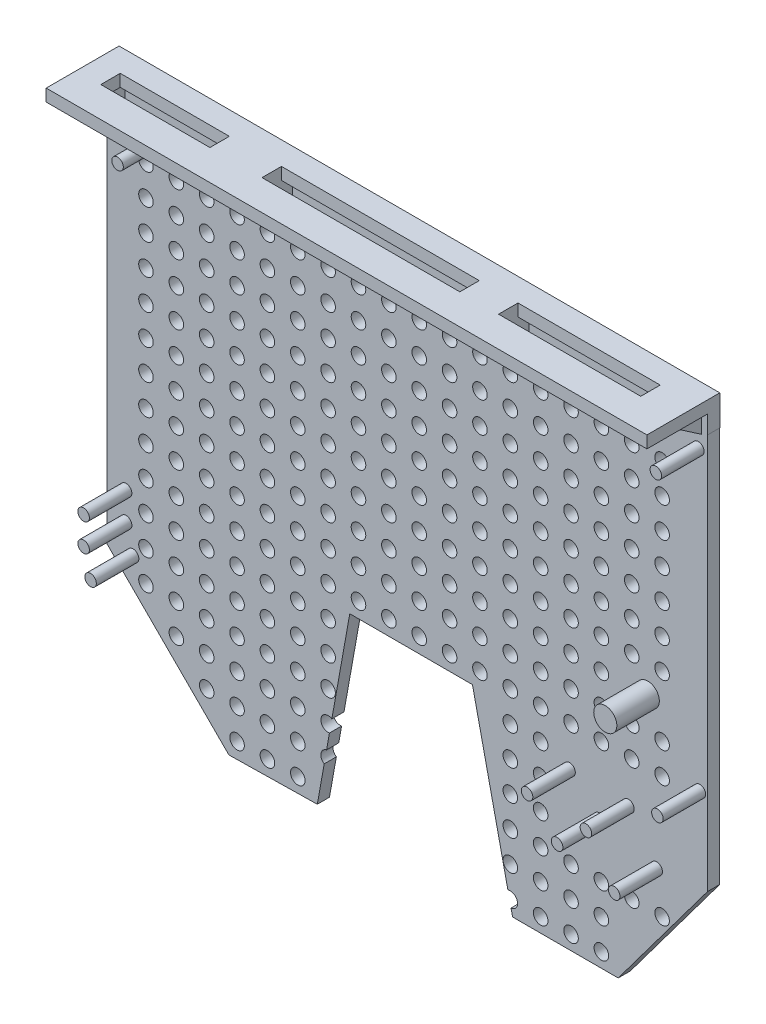
SolidWorks part; units mm, degrees
ref_plane "前视基准面" through (0, 0, 0) normal (0, 0, 1) x (1, 0, 0)
ref_plane "上视基准面" through (0, 0, 0) normal (0, 1, 0) x (1, 0, 0)
ref_plane "右视基准面" through (0, 0, 0) normal (1, 0, 0) x (0, 0, -1)
sketch "草图1" plane through (0, 0, 0) normal (0, 0, 1) x (1, 0, 0)
  line B0 (-29.0704, -45.0482) -> (-8.9847, -65.1339)
  line B1 (-29.0704, 19.934) -> (69.8393, 19.934)
  line B2 (-29.0704, 19.934) -> (-29.0704, -45.0482)
  line B3 (69.8393, 19.934) -> (69.8393, -45.2054)
  line B4 (5.5774, -64.8844) -> (10.922, -35.0394)
  line B5 (10.922, -35.0394) -> (31.1275, -35.0494)
  line B6 (31.1275, -35.0494) -> (37.7318, -64.8844)
  line B7 (37.7318, -64.8844) -> (55.1271, -64.8881)
  line B8 (55.1271, -64.8881) -> (69.8393, -45.2054)
  line B9 (-8.9847, -65.1339) -> (5.5774, -64.8844)
  circle B10 centre (-24.765, -44.5771) radius 0.95
sketch_block_instance "块-草图1-1"
sketch_block "块-草图1"
extrude "凸台-拉伸1" add sketch "草图1" along normal blind 2 contours B2 B0 B9 B4 B5 B6 B7 B8 B3 B1
sketch "草图2" plane through (0, 0, 0) normal (0, 0, 1) x (1, 0, 0)
  line B0 (-29.0704, -45.0482) -> (-8.9847, -65.1339)
  line B1 (-29.0704, 19.934) -> (69.8393, 19.934)
  line B2 (-29.0704, 19.934) -> (-29.0704, -45.0482)
  line B3 (69.8393, 19.934) -> (69.8393, -45.2054)
  line B4 (5.5774, -64.8844) -> (10.922, -35.0394)
  line B5 (10.922, -35.0394) -> (31.1275, -35.0494)
  line B6 (31.1275, -35.0494) -> (37.7318, -64.8844)
  line B7 (37.7318, -64.8844) -> (55.1271, -64.8881)
  line B8 (55.1271, -64.8881) -> (69.8393, -45.2054)
  line B9 (-8.9847, -65.1339) -> (5.5774, -64.8844)
  circle B10 centre (-20.32, 17.018) radius 0.95
  circle B11 centre (68.3261, 17.272) radius 0.95
  circle B12 centre (60.0001, -22) radius 1.9
  circle B13 centre (68.5801, -31.4961) radius 0.95
  circle B14 centre (-25.9081, -35.8141) radius 0.95
  circle B15 centre (-25.9081, -40.3861) radius 0.95
  circle B16 centre (-24.765, -44.5771) radius 0.95
  circle B17 centre (56.8115, -39.4971) radius 0.95
  circle B18 centre (47.1171, -39.1161) radius 0.95
  circle B19 centre (52.0701, -43.8151) radius 0.95
  circle B20 centre (61.4681, -46.1011) radius 0.95
sketch_block_instance "块-草图1-2"
extrude "凸台-拉伸2" add sketch "草图2" along normal blind 9 contours B10 | B11 | B12 | B13 | B17 | B19 | B18 | B16 | B14 | B15 | B20
sketch "草图3" plane through (0, 0, 0) normal (0, 0, 1) x (1, 0, 0)
  line L1 (-29.0704, 19.934) -> (69.8586, 19.934)
  line L2 (-29.0704, 19.934) -> (-29.0704, 24.934)
  line L3 (-29.0704, 24.934) -> (69.8586, 24.934)
  line L4 (69.8586, 19.934) -> (69.8586, 24.934)
  line B0 (-29.0704, -45.0482) -> (-8.9847, -65.1339)
  line B1 (-29.0704, 19.934) -> (69.8393, 19.934)
  line B2 (-29.0704, 19.934) -> (-29.0704, -45.0482)
  line B3 (69.8393, 19.934) -> (69.8393, -45.2054)
  line B4 (5.5774, -64.8844) -> (10.922, -35.0394)
  line B5 (10.922, -35.0394) -> (31.1275, -35.0494)
  line B6 (31.1275, -35.0494) -> (37.7318, -64.8844)
  line B7 (37.7318, -64.8844) -> (55.1271, -64.8881)
  line B8 (55.1271, -64.8881) -> (69.8393, -45.2054)
  line B9 (-8.9847, -65.1339) -> (5.5774, -64.8844)
  circle B10 centre (-20.32, 17.018) radius 0.95
  circle B11 centre (68.3261, 17.272) radius 0.95
  circle B12 centre (60.0001, -22) radius 1.9
  circle B13 centre (68.5801, -31.4961) radius 0.95
  circle B14 centre (-25.9081, -35.8141) radius 0.95
  circle B15 centre (-25.9081, -40.3861) radius 0.95
  circle B16 centre (-24.765, -44.5771) radius 0.95
  circle B17 centre (56.8115, -39.4971) radius 0.95
  circle B18 centre (47.1171, -39.1161) radius 0.95
  circle B19 centre (52.0701, -43.8151) radius 0.95
  circle B20 centre (61.4681, -46.1011) radius 0.95
  dimension "D1" = 5
sketch_block_instance "块-草图1-3"
extrude "凸台-拉伸3" add sketch "草图3" along normal blind 2 contours L3 L4 L1 L2
sketch "草图4" plane through (0, 0, 0) normal (0, 0, 1) x (1, 0, 0)
  line L1 (-29.0704, 19.934) -> (69.8586, 19.934)
  line L2 (-29.0704, 19.934) -> (-29.0704, 24.934)
  line L3 (-29.0704, 24.934) -> (69.8586, 24.934)
  line L4 (69.8586, 19.934) -> (69.8586, 24.934)
  line L5 (69.8586, 24.934) -> (-29.0704, 24.934)
  line L6 (69.8586, 24.934) -> (69.8586, 22.934)
  line L7 (69.8586, 22.934) -> (-29.0704, 22.934)
  line L8 (-29.0704, 24.934) -> (-29.0704, 22.934)
  line B0 (-29.0704, -45.0482) -> (-8.9847, -65.1339)
  line B1 (-29.0704, 19.934) -> (69.8393, 19.934)
  line B2 (-29.0704, 19.934) -> (-29.0704, -45.0482)
  line B3 (69.8393, 19.934) -> (69.8393, -45.2054)
  line B4 (5.5774, -64.8844) -> (10.922, -35.0394)
  line B5 (10.922, -35.0394) -> (31.1275, -35.0494)
  line B6 (31.1275, -35.0494) -> (37.7318, -64.8844)
  line B7 (37.7318, -64.8844) -> (55.1271, -64.8881)
  line B8 (55.1271, -64.8881) -> (69.8393, -45.2054)
  line B9 (-8.9847, -65.1339) -> (5.5774, -64.8844)
  circle B10 centre (-20.32, 17.018) radius 0.95
  circle B11 centre (68.3261, 17.272) radius 0.95
  circle B12 centre (60.0001, -22) radius 1.9
  circle B13 centre (68.5801, -31.4961) radius 0.95
  circle B14 centre (-25.9081, -35.8141) radius 0.95
  circle B15 centre (-25.9081, -40.3861) radius 0.95
  circle B16 centre (-24.765, -44.5771) radius 0.95
  circle B17 centre (56.8115, -39.4971) radius 0.95
  circle B18 centre (47.1171, -39.1161) radius 0.95
  circle B19 centre (52.0701, -43.8151) radius 0.95
  circle B20 centre (61.4681, -46.1011) radius 0.95
  dimension "D1" = 5
  dimension "D2" = 2
sketch_block_instance "块-草图1-4"
extrude "凸台-拉伸4" add sketch "草图4" along normal blind 12 contours L6 L7 L8 L3
ref_plane "基准面2" through (0, 24.934, 0) normal (0, 1, 0) x (1, 0, 0)
sketch "草图6" plane through (0, 24.934, 0) normal (0, 1, 0) x (1, 0, 0)
  line L0 (69.8586, -12) -> (69.8586, 0) construction
  line L1 (-29.0704, -12) -> (69.8586, -12)
  line L2 (-29.0704, -12) -> (-29.0704, -7)
  line L3 (-29.0704, -7) -> (69.8586, -7)
  line L4 (69.8586, -12) -> (69.8586, -7)
  line L6 (1.4708, -7) -> (34.0493, -7)
  line L7 (1.4708, -7) -> (1.4708, -3.8)
  line L8 (1.4708, -3.8) -> (34.0493, -3.8)
  line L9 (34.0493, -7) -> (34.0493, -3.8)
  line L10 (40.4259, -7) -> (63.8453, -7)
  line L11 (40.4259, -7) -> (40.4259, -3.8)
  line L12 (40.4259, -3.8) -> (63.8453, -3.8)
  line L13 (63.8453, -7) -> (63.8453, -3.8)
  line L14 (-7.1086, -7) -> (-25.0789, -7)
  line L15 (-7.1086, -7) -> (-7.1086, -3.8)
  line L16 (-7.1086, -3.8) -> (-25.0789, -3.8)
  line L17 (-25.0789, -7) -> (-25.0789, -3.8)
  dimension "D1" = 5
  dimension "D2" = 3.2
extrude "切除-拉伸3" cut sketch "草图6" against normal up to next contours L11 L12 L13 L10 | L7 L8 L9 L6 | L16 L17 L14 L15
sketch "草图8" plane through (0, 0, 0) normal (0, 0, 1) x (1, 0, 0)
  circle A38 centre (-12.6417, 17.4584) radius 1.2
  circle A39 centre (-7.6417, 17.4584) radius 1.2
  circle A40 centre (-2.6417, 17.4584) radius 1.2
  circle A41 centre (2.3583, 17.4584) radius 1.2
  circle A42 centre (7.3583, 17.4584) radius 1.2
  circle A43 centre (12.3583, 17.4584) radius 1.2
  circle A44 centre (17.3583, 17.4584) radius 1.2
  circle A45 centre (22.3583, 17.4584) radius 1.2
  circle A46 centre (27.3583, 17.4584) radius 1.2
  circle A47 centre (32.3583, 17.4584) radius 1.2
  circle A48 centre (37.3583, 17.4584) radius 1.2
  circle A49 centre (42.3583, 17.4584) radius 1.2
  circle A50 centre (47.3583, 17.4584) radius 1.2
  circle A51 centre (52.3583, 17.4584) radius 1.2
  circle A52 centre (57.3583, 17.4584) radius 1.2
  circle A53 centre (62.3583, 17.4584) radius 1.2
  circle A54 centre (-17.6417, 12.4584) radius 1.2
  circle A55 centre (-12.6417, 12.4584) radius 1.2
  circle A56 centre (-7.6417, 12.4584) radius 1.2
  circle A57 centre (-2.6417, 12.4584) radius 1.2
  circle A58 centre (2.3583, 12.4584) radius 1.2
  circle A59 centre (7.3583, 12.4584) radius 1.2
  circle A60 centre (12.3583, 12.4584) radius 1.2
  circle A61 centre (17.3583, 12.4584) radius 1.2
  circle A62 centre (22.3583, 12.4584) radius 1.2
  circle A63 centre (27.3583, 12.4584) radius 1.2
  circle A64 centre (32.3583, 12.4584) radius 1.2
  circle A65 centre (37.3583, 12.4584) radius 1.2
  circle A66 centre (42.3583, 12.4584) radius 1.2
  circle A67 centre (47.3583, 12.4584) radius 1.2
  circle A68 centre (52.3583, 12.4584) radius 1.2
  circle A69 centre (57.3583, 12.4584) radius 1.2
  circle A70 centre (62.3583, 12.4584) radius 1.2
  circle A71 centre (-17.6417, 7.4584) radius 1.2
  circle A72 centre (-12.6417, 7.4584) radius 1.2
  circle A73 centre (-7.6417, 7.4584) radius 1.2
  circle A74 centre (-2.6417, 7.4584) radius 1.2
  circle A75 centre (2.3583, 7.4584) radius 1.2
  circle A76 centre (7.3583, 7.4584) radius 1.2
  circle A77 centre (12.3583, 7.4584) radius 1.2
  circle A78 centre (17.3583, 7.4584) radius 1.2
  circle A79 centre (22.3583, 7.4584) radius 1.2
  circle A80 centre (27.3583, 7.4584) radius 1.2
  circle A81 centre (32.3583, 7.4584) radius 1.2
  circle A82 centre (37.3583, 7.4584) radius 1.2
  circle A83 centre (42.3583, 7.4584) radius 1.2
  circle A84 centre (47.3583, 7.4584) radius 1.2
  circle A85 centre (52.3583, 7.4584) radius 1.2
  circle A86 centre (57.3583, 7.4584) radius 1.2
  circle A87 centre (62.3583, 7.4584) radius 1.2
  circle A88 centre (-17.6417, 2.4584) radius 1.2
  circle A89 centre (-12.6417, 2.4584) radius 1.2
  circle A90 centre (-7.6417, 2.4584) radius 1.2
  circle A91 centre (-2.6417, 2.4584) radius 1.2
  circle A92 centre (2.3583, 2.4584) radius 1.2
  circle A93 centre (7.3583, 2.4584) radius 1.2
  circle A94 centre (12.3583, 2.4584) radius 1.2
  circle A95 centre (17.3583, 2.4584) radius 1.2
  circle A96 centre (22.3583, 2.4584) radius 1.2
  circle A97 centre (27.3583, 2.4584) radius 1.2
  circle A98 centre (32.3583, 2.4584) radius 1.2
  circle A99 centre (37.3583, 2.4584) radius 1.2
  circle A100 centre (42.3583, 2.4584) radius 1.2
  circle A101 centre (47.3583, 2.4584) radius 1.2
  circle A102 centre (52.3583, 2.4584) radius 1.2
  circle A103 centre (57.3583, 2.4584) radius 1.2
  circle A104 centre (62.3583, 2.4584) radius 1.2
  circle A105 centre (-17.6417, -2.5416) radius 1.2
  circle A106 centre (-12.6417, -2.5416) radius 1.2
  circle A107 centre (-7.6417, -2.5416) radius 1.2
  circle A108 centre (-2.6417, -2.5416) radius 1.2
  circle A109 centre (2.3583, -2.5416) radius 1.2
  circle A110 centre (7.3583, -2.5416) radius 1.2
  circle A111 centre (12.3583, -2.5416) radius 1.2
  circle A112 centre (17.3583, -2.5416) radius 1.2
  circle A113 centre (22.3583, -2.5416) radius 1.2
  circle A114 centre (27.3583, -2.5416) radius 1.2
  circle A115 centre (32.3583, -2.5416) radius 1.2
  circle A116 centre (37.3583, -2.5416) radius 1.2
  circle A117 centre (42.3583, -2.5416) radius 1.2
  circle A118 centre (47.3583, -2.5416) radius 1.2
  circle A119 centre (52.3583, -2.5416) radius 1.2
  circle A120 centre (57.3583, -2.5416) radius 1.2
  circle A121 centre (62.3583, -2.5416) radius 1.2
  circle A122 centre (-17.6417, -7.5416) radius 1.2
  circle A123 centre (-12.6417, -7.5416) radius 1.2
  circle A124 centre (-7.6417, -7.5416) radius 1.2
  circle A125 centre (-2.6417, -7.5416) radius 1.2
  circle A126 centre (2.3583, -7.5416) radius 1.2
  circle A127 centre (7.3583, -7.5416) radius 1.2
  circle A128 centre (12.3583, -7.5416) radius 1.2
  circle A129 centre (17.3583, -7.5416) radius 1.2
  circle A130 centre (22.3583, -7.5416) radius 1.2
  circle A131 centre (27.3583, -7.5416) radius 1.2
  circle A132 centre (32.3583, -7.5416) radius 1.2
  circle A133 centre (37.3583, -7.5416) radius 1.2
  circle A134 centre (42.3583, -7.5416) radius 1.2
  circle A135 centre (47.3583, -7.5416) radius 1.2
  circle A136 centre (52.3583, -7.5416) radius 1.2
  circle A137 centre (57.3583, -7.5416) radius 1.2
  circle A138 centre (62.3583, -7.5416) radius 1.2
  circle A139 centre (-17.6417, -12.5416) radius 1.2
  circle A140 centre (-12.6417, -12.5416) radius 1.2
  circle A141 centre (-7.6417, -12.5416) radius 1.2
  circle A142 centre (-2.6417, -12.5416) radius 1.2
  circle A143 centre (2.3583, -12.5416) radius 1.2
  circle A144 centre (7.3583, -12.5416) radius 1.2
  circle A145 centre (12.3583, -12.5416) radius 1.2
  circle A146 centre (17.3583, -12.5416) radius 1.2
  circle A147 centre (22.3583, -12.5416) radius 1.2
  circle A148 centre (27.3583, -12.5416) radius 1.2
  circle A149 centre (32.3583, -12.5416) radius 1.2
  circle A150 centre (37.3583, -12.5416) radius 1.2
  circle A151 centre (42.3583, -12.5416) radius 1.2
  circle A152 centre (47.3583, -12.5416) radius 1.2
  circle A153 centre (52.3583, -12.5416) radius 1.2
  circle A154 centre (57.3583, -12.5416) radius 1.2
  circle A155 centre (62.3583, -12.5416) radius 1.2
  circle A156 centre (-17.6417, -17.5416) radius 1.2
  circle A157 centre (-12.6417, -17.5416) radius 1.2
  circle A158 centre (-7.6417, -17.5416) radius 1.2
  circle A159 centre (-2.6417, -17.5416) radius 1.2
  circle A160 centre (2.3583, -17.5416) radius 1.2
  circle A161 centre (7.3583, -17.5416) radius 1.2
  circle A162 centre (12.3583, -17.5416) radius 1.2
  circle A163 centre (17.3583, -17.5416) radius 1.2
  circle A164 centre (22.3583, -17.5416) radius 1.2
  circle A165 centre (27.3583, -17.5416) radius 1.2
  circle A166 centre (32.3583, -17.5416) radius 1.2
  circle A167 centre (37.3583, -17.5416) radius 1.2
  circle A168 centre (42.3583, -17.5416) radius 1.2
  circle A169 centre (47.3583, -17.5416) radius 1.2
  circle A170 centre (52.3583, -17.5416) radius 1.2
  circle A171 centre (57.3583, -17.5416) radius 1.2
  circle A172 centre (62.3583, -17.5416) radius 1.2
  circle A173 centre (-17.6417, -22.5416) radius 1.2
  circle A174 centre (-12.6417, -22.5416) radius 1.2
  circle A175 centre (-7.6417, -22.5416) radius 1.2
  circle A176 centre (-2.6417, -22.5416) radius 1.2
  circle A177 centre (2.3583, -22.5416) radius 1.2
  circle A178 centre (7.3583, -22.5416) radius 1.2
  circle A179 centre (12.3583, -22.5416) radius 1.2
  circle A180 centre (17.3583, -22.5416) radius 1.2
  circle A181 centre (22.3583, -22.5416) radius 1.2
  circle A182 centre (27.3583, -22.5416) radius 1.2
  circle A183 centre (32.3583, -22.5416) radius 1.2
  circle A184 centre (37.3583, -22.5416) radius 1.2
  circle A185 centre (42.3583, -22.5416) radius 1.2
  circle A186 centre (47.3583, -22.5416) radius 1.2
  circle A187 centre (52.3583, -22.5416) radius 1.2
  circle A190 centre (-17.6417, -27.5416) radius 1.2
  circle A191 centre (-12.6417, -27.5416) radius 1.2
  circle A192 centre (-7.6417, -27.5416) radius 1.2
  circle A193 centre (-2.6417, -27.5416) radius 1.2
  circle A194 centre (2.3583, -27.5416) radius 1.2
  circle A195 centre (7.3583, -27.5416) radius 1.2
  circle A196 centre (12.3583, -27.5416) radius 1.2
  circle A197 centre (17.3583, -27.5416) radius 1.2
  circle A198 centre (22.3583, -27.5416) radius 1.2
  circle A199 centre (27.3583, -27.5416) radius 1.2
  circle A200 centre (32.3583, -27.5416) radius 1.2
  circle A201 centre (37.3583, -27.5416) radius 1.2
  circle A202 centre (42.3583, -27.5416) radius 1.2
  circle A203 centre (47.3583, -27.5416) radius 1.2
  circle A204 centre (52.3583, -27.5416) radius 1.2
  circle A205 centre (57.3583, -27.5416) radius 1.2
  circle A206 centre (62.3583, -27.5416) radius 1.2
  circle A207 centre (-17.6417, -32.5416) radius 1.2
  circle A208 centre (-12.6417, -32.5416) radius 1.2
  circle A209 centre (-7.6417, -32.5416) radius 1.2
  circle A210 centre (-2.6417, -32.5416) radius 1.2
  circle A211 centre (2.3583, -32.5416) radius 1.2
  circle A212 centre (7.3583, -32.5416) radius 1.2
  circle A213 centre (12.3583, -32.5416) radius 1.2
  circle A214 centre (17.3583, -32.5416) radius 1.2
  circle A215 centre (22.3583, -32.5416) radius 1.2
  circle A216 centre (27.3583, -32.5416) radius 1.2
  circle A217 centre (32.3583, -32.5416) radius 1.2
  circle A218 centre (37.3583, -32.5416) radius 1.2
  circle A219 centre (42.3583, -32.5416) radius 1.2
  circle A220 centre (47.3583, -32.5416) radius 1.2
  circle A221 centre (52.3583, -32.5416) radius 1.2
  circle A222 centre (57.3583, -32.5416) radius 1.2
  circle A223 centre (62.3583, -32.5416) radius 1.2
  circle A224 centre (-17.6417, -37.5416) radius 1.2
  circle A225 centre (-12.6417, -37.5416) radius 1.2
  circle A226 centre (-7.6417, -37.5416) radius 1.2
  circle A227 centre (-2.6417, -37.5416) radius 1.2
  circle A228 centre (2.3583, -37.5416) radius 1.2
  circle A229 centre (7.3583, -37.5416) radius 1.2
  circle A235 centre (37.3583, -37.5416) radius 1.2
  circle A236 centre (42.3583, -37.5416) radius 1.2
  circle A241 centre (-17.6417, -42.5416) radius 1.2
  circle A242 centre (-12.6417, -42.5416) radius 1.2
  circle A243 centre (-7.6417, -42.5416) radius 1.2
  circle A244 centre (-2.6417, -42.5416) radius 1.2
  circle A245 centre (2.3583, -42.5416) radius 1.2
  circle A246 centre (7.3583, -42.5416) radius 1.2
  circle A252 centre (37.3583, -42.5416) radius 1.2
  circle A253 centre (42.3583, -42.5416) radius 1.2
  circle A258 centre (-17.6417, -47.5416) radius 1.2
  circle A259 centre (-12.6417, -47.5416) radius 1.2
  circle A260 centre (-7.6417, -47.5416) radius 1.2
  circle A261 centre (-2.6417, -47.5416) radius 1.2
  circle A262 centre (2.3583, -47.5416) radius 1.2
  circle A263 centre (7.3583, -47.5416) radius 1.2
  circle A269 centre (37.3583, -47.5416) radius 1.2
  circle A270 centre (42.3583, -47.5416) radius 1.2
  circle A275 centre (-17.6417, -52.5416) radius 1.2
  circle A276 centre (-12.6417, -52.5416) radius 1.2
  circle A277 centre (-7.6417, -52.5416) radius 1.2
  circle A278 centre (-2.6417, -52.5416) radius 1.2
  circle A279 centre (2.3583, -52.5416) radius 1.2
  circle A280 centre (7.3583, -52.5416) radius 1.2
  circle A286 centre (37.3583, -52.5416) radius 1.2
  circle A287 centre (42.3583, -52.5416) radius 1.2
  circle A288 centre (47.3583, -52.5416) radius 1.2
  circle A289 centre (52.3583, -52.5416) radius 1.2
  circle A290 centre (57.3583, -52.5416) radius 1.2
  circle A291 centre (62.3583, -52.5416) radius 1.2
  circle A293 centre (-12.6417, -57.5416) radius 1.2
  circle A294 centre (-7.6417, -57.5416) radius 1.2
  circle A295 centre (-2.6417, -57.5416) radius 1.2
  circle A296 centre (2.3583, -57.5416) radius 1.2
  circle A297 centre (7.3583, -57.5416) radius 1.2
  circle A303 centre (37.3583, -57.5416) radius 1.2
  circle A304 centre (42.3583, -57.5416) radius 1.2
  circle A305 centre (47.3583, -57.5416) radius 1.2
  circle A306 centre (52.3583, -57.5416) radius 1.2
  circle A311 centre (-7.6417, -62.5416) radius 1.2
  circle A312 centre (-2.6417, -62.5416) radius 1.2
  circle A313 centre (2.3583, -62.5416) radius 1.2
  circle A314 centre (7.3583, -62.5416) radius 1.2
  circle A320 centre (37.3583, -62.5416) radius 1.2
  circle A321 centre (42.3583, -62.5416) radius 1.2
  circle A322 centre (47.3583, -62.5416) radius 1.2
  circle A323 centre (52.3583, -62.5416) radius 1.2
  circle A327 centre (-22.6417, 12.4584) radius 1.2
  circle A328 centre (-22.6417, 7.4584) radius 1.2
  circle A329 centre (-22.6417, 2.4584) radius 1.2
  circle A330 centre (-22.6417, -2.5416) radius 1.2
  circle A331 centre (-22.6417, -7.5416) radius 1.2
  circle A332 centre (-22.6417, -12.5416) radius 1.2
  circle A333 centre (-22.6417, -17.5416) radius 1.2
  circle A334 centre (-22.6417, -22.5416) radius 1.2
  circle A335 centre (-22.6417, -27.5416) radius 1.2
  circle A336 centre (-22.6417, -32.5416) radius 1.2
  circle A337 centre (-22.6417, -37.5416) radius 1.2
  circle A338 centre (-22.6417, -42.5416) radius 1.2
  circle A339 centre (-22.6417, -47.5416) radius 1.2
extrude "切除-拉伸6" cut sketch "草图8" along direction (0, 0, -1) on the side against the normal through all and the other way through all
ref_plane "基准面3" through (-29.0704, 0, 0) normal (-1, 0, 0) x (0, 0, 1)
sketch "草图11" plane through (-29.0704, 0, 0) normal (-1, 0, 0) x (0, 0, 1)
  line L0 (7, 22.934) -> (2, 19.509)
  line L1 (12, 22.934) -> (2, 22.934) construction
  line L2 (2, 22.934) -> (2, -45.0482) construction
rib "筋11" sketch "草图11" sketch "草图11" thickness 3 extrusion direction parallel to sketch draft on no parameters "D1"=3
ref_plane "基准面4" through (1.4708, 0, 0) normal (-1, 0, 0) x (0, 0, 1)
sketch "草图12" plane through (1.4708, 0, 0) normal (-1, 0, 0) x (0, 0, 1)
  line L0 (7, 22.934) -> (2, 19.509)
rib "筋13" sketch "草图12" sketch "草图12" thickness 7 parameters "D1"=7
ref_plane "基准面6" through (40.4259, 0, 0) normal (-1, 0, 0) x (0, 0, 1)
sketch "草图13" plane through (40.4259, 0, 0) normal (-1, 0, 0) x (0, 0, 1)
  line L0 (7, 22.934) -> (2, 19.509)
rib "筋14" sketch "草图13" sketch "草图13" thickness 6 parameters "D1"=6
ref_plane "基准面8" through (63.8453, 0, 0) normal (-1, 0, 0) x (0, 0, 1)
sketch "草图15" plane through (63.8453, 0, 0) normal (-1, 0, 0) x (0, 0, 1)
  line L0 (7, 22.934) -> (2, 19.509)
rib "筋33" sketch "草图15" sketch "草图15" thickness 5 extrusion direction parallel to sketch draft on no parameters "D1"=5
